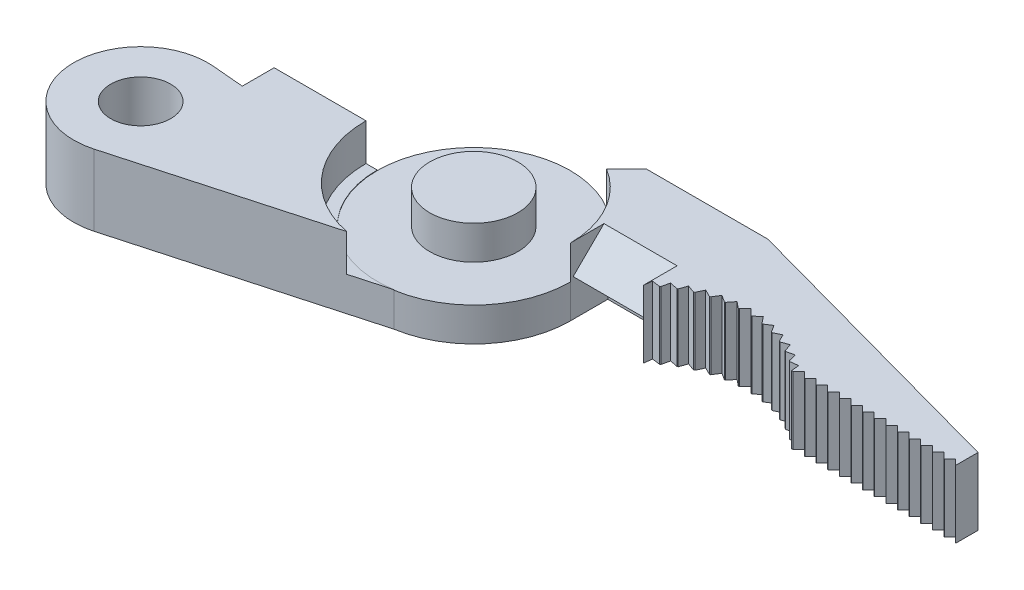
SolidWorks part; units mm, degrees
ref_plane "Front Plane" through (0, 0, 0) normal (0, 0, 1) x (1, 0, 0)
ref_plane "Top Plane" through (0, 0, 0) normal (0, 1, 0) x (1, 0, 0)
ref_plane "Right Plane" through (0, 0, 0) normal (1, 0, 0) x (0, 0, -1)
sketch "Sketch1" plane through (0, 0, 0) normal (0, 1, 0) x (1, 0, 0)
  circle A0 centre (0, 0) radius 6.5405
  circle A1 centre (0, 0) radius 2.9845
  dimension "D1" = 13.081
  dimension "D2" = 5.969
extrude "Boss-Extrude1" add sketch "Sketch1" along normal blind 4.826
sketch "Sketch2" plane through (0, 0, 0) normal (0, 1, 0) x (1, 0, 0)
  line L0 (-6.5405, 0) -> (-13.5255, 0)
  line L1 (-13.5255, 0) -> (-13.5255, -2.159)
  line L2 (-15.6763, -1.9708) -> (-13.5255, -2.159)
  line L3 (1.0584, -6.4543) -> (-14.8567, -10.8736)
  circle A1 centre (-16.0722, -6.4964) radius 2.032
  circle A2 centre (0, 0) radius 2.9845 construction
  arc A3 (-15.6763, -1.9708) -> (-14.8567, -10.8736) centre (-16.0722, -6.4964) ccw
  arc A4 (-6.5405, 0) -> (1.0584, -6.4543) centre (0, 0) ccw
  dimension "D1" = 4.064
  dimension "D6" = 17.3355
  dimension "D2" = 6.985
  dimension "D3" = 2.159
  dimension "D4" = 2.159
  dimension "D5" = 85
extrude "Boss-Extrude2" add sketch "Sketch2" along normal up to surface (4.826 mm away) up to face at (0, 4.826, 6.5405)
hole_wizard "#43 (0.089) Diameter Hole1" positions "Sketch6" profile "Sketch7" hole size "#43" standard "ANSI Inch"
sketch "Sketch6" plane through (0, 0, 0) normal (0, 0, -1) x (-1, 0, 0)
  line L0 (13.5255, 4.826) -> (13.5255, 0) construction
  line L1 (6.5405, 0) -> (13.5255, 0) construction
  point P0 (10.033, 2.413)
  dimension "D1" = 3.4925
  dimension "D2" = 2.413
sketch "Sketch7" plane through (-10.033, 2.413, 0) normal (1, 0, 0) x (0, 1, 0)
  line L0 (0, 0) -> (0, 2.7112)
  line L1 (0, 2.7112) -> (1.1303, 2.032)
  line L2 (1.1303, 2.032) -> (1.1303, 0)
  line L5 (1.1303, 0) -> (0, 0)
  line L10 (0, 2.7112) -> (-1.1303, 2.032) construction
  line L11 (0, -6.35) -> (0, 107.95) construction
  dimension "Hole Dia." = 2.2606
  dimension "Hole Depth" = 2.032
  dimension "Drill Angle" = 118
sketch "Sketch8" plane through (0, 0, 0) normal (0, 1, 0) x (1, 0, 0)
  line L0 (13.0016, 6.9215) -> (32.639, 1.524)
  line L1 (32.639, 1.524) -> (32.639, 0)
  line L2 (32.639, 0) -> (21.5265, 0)
  line L3 (13.0016, 6.9215) -> (4.7466, 6.9215)
  line L4 (4.7466, 6.9215) -> (3.4077, 5.5826)
  line L5 (6.5405, 0) -> (11.4935, 0)
  arc A2 (1.0584, -6.4543) -> (-6.5405, 0) centre (0, 0) ccw construction
  arc A4 (21.5265, 0) -> (11.4935, 0) centre (16.51, -5.7358) ccw
  arc A5 (6.5405, 0) -> (3.4077, 5.5826) centre (0, 0) ccw
  dimension "D1" = 0.381
  dimension "D8" = 15.24
  dimension "D2" = 1.524
  dimension "D3" = 8.255
  dimension "D4" = 32.639
  dimension "D5" = 225
  dimension "D6" = 11.1125
  dimension "D7" = 4.953
extrude "Boss-Extrude3" add sketch "Sketch8" along normal up to surface (4.826 mm away) up to face at (-10.2367, 4.826, 2.2894)
sketch "Sketch9" plane through (0, 4.826, 0) normal (0, 1, 0) x (1, 0, 0)
  line L10 (-7.3025, 0) -> (-6.5405, 0)
  line L11 (-1.463, -7.1544) -> (1.0584, -6.4543)
  line L12 (-14.8567, -10.8736) -> (1.0584, -6.4543) construction
  line L32 (33.401, -0.762) -> (33.401, 2.1048)
  arc A4 (-7.3025, 0) -> (-1.463, -7.1544) centre (0, 0) ccw
  arc A5 (-6.5405, 0) -> (1.0584, -6.4543) centre (0, 0) ccw
  arc A6 (3.4077, 5.5826) -> (-6.5405, 0) centre (0, 0) ccw construction
  arc A7 (1.0584, -6.4543) -> (6.5405, 0) centre (0, 0) ccw construction
  line M26 (-6.5405, 0) -> (-13.5255, 0)
  line M30 (-14.8567, -10.8736) -> (1.0584, -6.4543)
  dimension "D1" = 0.762
  dimension "D2" = 6.5405
  dimension "D3" = 2.6168
extrude "Cut-Extrude1" cut sketch "Sketch9" against normal blind 2.5082 contours A5 A4 M26 M30 region at (-6.9215, 4.826, 0.11)
sketch "Sketch10" plane through (0, 4.826, 0) normal (0, 1, 0) x (1, 0, 0)
  line L0 (32.639, 0) -> (32.258, 0.381)
  line L1 (32.258, 0.381) -> (31.877, 0)
  line L3 (21.5265, 0) -> (32.639, 0) construction
  line L4 (31.877, 0) -> (32.639, 0)
  dimension "D1" = 0.381
extrude "Cut-Extrude2" cut sketch "Sketch10" against normal through all
pattern_linear "LPattern1" count 14 spacing 0.7874 along (-1, 0, 0) of "Cut-Extrude2"
sketch "Sketch11" plane through (0, 4.826, 0) normal (0, 1, 0) x (1, 0, 0)
  line L0 (21.5265, 0) -> (21.4646, 0.5466)
  line L1 (21.4646, 0.5466) -> (20.9187, 0.4794)
  arc A0 (21.5265, 0) -> (11.4935, 0) centre (16.51, -5.7358) ccw construction
  arc A1 (21.5265, 0) -> (20.9187, 0.4794) centre (16.51, -5.7358) ccw
  dimension "D1" = 8.001
extrude "Cut-Extrude3" cut sketch "Sketch11" against normal through all
pattern_circular "CirPattern1" count 13 over 76.5 about axis through (16.51, 4.826, 5.7358) along (0, -1, 0) of "Cut-Extrude3" reverse direction yes
sketch "Sketch13" plane through (0, 4.826, 0) normal (0, 1, 0) x (1, 0, 0)
  line L0 (11.4935, 0) -> (11.4935, 2.54)
  line L1 (11.4935, 2.54) -> (6.5405, 2.54)
  line L2 (6.5405, 2.54) -> (6.5405, 0)
  line L3 (6.5405, 0) -> (11.4935, 0)
  dimension "D1" = 2.54
extrude "Cut-Extrude5" cut sketch "Sketch13" against normal blind 2.5082
sketch "Sketch14" plane through (6.5405, 0, 0) normal (1, 0, 0) x (0, 0, -1)
  line L0 (0, 2.3178) -> (2.54, 4.826)
  line L1 (2.54, 4.826) -> (2.54, 2.3177)
  line L2 (2.54, 2.3177) -> (2.54, 4.826) construction
  line L3 (2.54, 2.3177) -> (0, 2.3178) construction
  line L4 (2.54, 2.3177) -> (0, 2.3178)
extrude "Boss-Extrude4" add sketch "Sketch14" along normal up to next
sketch "Sketch15" plane through (0, 0, 0) normal (0, -1, 0) x (1, 0, 0)
  line L0 (6.5405, 0) -> (6.5405, -2.54)
  line L1 (6.5405, 0) -> (11.4935, 0) construction
  line L2 (6.5405, -2.54) -> (11.52, -2.54)
  line L3 (11.52, -2.54) -> (11.4935, 0)
  line L4 (11.4935, 0) -> (6.5405, 0)
  arc A0 (6.5405, 0) -> (1.0584, 6.4543) centre (0, 0) ccw construction
  dimension "D1" = 2.54
extrude "Cut-Extrude6" cut sketch "Sketch15" against normal blind 2.5082
sketch "Sketch16" plane through (0, 4.826, 0) normal (0, 1, 0) x (1, 0, 0)
  circle A0 centre (0, 0) radius 6.5405
extrude "Cut-Extrude7" cut sketch "Sketch16" against normal blind 2.54
sketch "Sketch18" plane through (0, 0, 0) normal (0, 1, 0) x (1, 0, 0)
  circle A0 centre (0, 0) radius 2.9845
extrude "Boss-Extrude5" add sketch "Sketch18" along normal blind 4.572
sketch "Sketch19" plane through (0, 4.826, 0) normal (0, 1, 0) x (1, 0, 0)
  line L76 (6.5405, 0) -> (6.5405, 2.54)
  line L77 (6.5405, 2.54) -> (11.4935, 2.54)
  line L78 (11.4935, 2.54) -> (11.4935, 0)
  line L79 (11.4935, 0) -> (11.4958, 0.002)
  line L80 (11.4958, 0.002) -> (11.5579, 0.5485)
  line L81 (11.5579, 0.5485) -> (12.1038, 0.4811)
  line L82 (12.1639, 0.5233) -> (12.2863, 1.0595)
  line L83 (12.2863, 1.0595) -> (12.8213, 0.9319)
  line L84 (12.8857, 0.9671) -> (13.0669, 1.4865)
  line L85 (13.0669, 1.4865) -> (13.5845, 1.3003)
  line L86 (13.6524, 1.3281) -> (13.8901, 1.8241)
  line L87 (13.8901, 1.8241) -> (14.3838, 1.5816)
  line L88 (14.4544, 1.6017) -> (14.7457, 2.0683)
  line L89 (14.7457, 2.0683) -> (15.2095, 1.7724)
  line L90 (15.2818, 1.7846) -> (15.6232, 2.2159)
  line L91 (15.6232, 2.2159) -> (16.0512, 1.8704)
  line L92 (16.1244, 1.8745) -> (16.5116, 2.2652)
  line L93 (16.5116, 2.2652) -> (16.8986, 1.8743)
  line L94 (16.9718, 1.8702) -> (17.4, 2.2156)
  line L95 (17.4, 2.2156) -> (17.7411, 1.7841)
  line L96 (17.8135, 1.7719) -> (18.2773, 2.0676)
  line L97 (18.2773, 2.0676) -> (18.5685, 1.6009)
  line L98 (18.6391, 1.5807) -> (19.1329, 1.8231)
  line L99 (19.1329, 1.8231) -> (19.3704, 1.327)
  line L100 (19.4383, 1.2991) -> (19.9559, 1.4851)
  line L101 (19.9559, 1.4851) -> (20.1369, 0.9657)
  line L102 (20.2013, 0.9305) -> (20.7364, 1.0579)
  line L103 (20.7364, 1.0579) -> (20.8586, 0.5215)
  line L104 (20.9187, 0.4794) -> (21.4646, 0.5466)
  line L105 (21.4646, 0.5466) -> (21.5265, 0)
  line L106 (21.5265, 0) -> (21.6408, 0)
  line L107 (21.6408, 0) -> (22.0218, 0.381)
  line L108 (22.0218, 0.381) -> (22.4028, 0)
  line L109 (22.4028, 0) -> (22.4282, 0)
  line L110 (22.4282, 0) -> (22.8092, 0.381)
  line L111 (22.8092, 0.381) -> (23.1902, 0)
  line L112 (23.1902, 0) -> (23.2156, 0)
  line L113 (23.2156, 0) -> (23.5966, 0.381)
  line L114 (23.5966, 0.381) -> (23.9776, 0)
  line L115 (23.9776, 0) -> (24.003, 0)
  line L116 (24.003, 0) -> (24.384, 0.381)
  line L117 (24.384, 0.381) -> (24.765, 0)
  line L118 (24.765, 0) -> (24.7904, 0)
  line L119 (24.7904, 0) -> (25.1714, 0.381)
  line L120 (25.1714, 0.381) -> (25.5524, 0)
  line L121 (25.5524, 0) -> (25.5778, 0)
  line L122 (25.5778, 0) -> (25.9588, 0.381)
  line L123 (25.9588, 0.381) -> (26.3398, 0)
  line L124 (26.3398, 0) -> (26.3652, 0)
  line L125 (26.3652, 0) -> (26.7462, 0.381)
  line L126 (26.7462, 0.381) -> (27.1272, 0)
  line L127 (27.1272, 0) -> (27.1526, 0)
  line L128 (27.1526, 0) -> (27.5336, 0.381)
  line L129 (27.5336, 0.381) -> (27.9146, 0)
  line L130 (27.9146, 0) -> (27.94, 0)
  line L131 (27.94, 0) -> (28.321, 0.381)
  line L132 (28.321, 0.381) -> (28.702, 0)
  line L133 (28.702, 0) -> (28.7274, 0)
  line L134 (28.7274, 0) -> (29.1084, 0.381)
  line L135 (29.1084, 0.381) -> (29.4894, 0)
  line L136 (29.4894, 0) -> (29.5148, 0)
  line L137 (29.5148, 0) -> (29.8958, 0.381)
  line L138 (29.8958, 0.381) -> (30.2768, 0)
  line L139 (30.2768, 0) -> (30.3022, 0)
  line L140 (30.3022, 0) -> (30.6832, 0.381)
  line L141 (30.6832, 0.381) -> (31.0642, 0)
  line L142 (31.0642, 0) -> (31.0896, 0)
  line L143 (31.0896, 0) -> (31.4706, 0.381)
  line L144 (31.4706, 0.381) -> (31.8516, 0)
  line L145 (31.8516, 0) -> (31.877, 0)
  line L146 (31.877, 0) -> (32.258, 0.381)
  line L147 (32.258, 0.381) -> (32.639, 0)
  line L148 (32.639, 0) -> (32.639, 1.524)
  line L149 (32.639, 1.524) -> (13.0016, 6.9215)
  line L150 (13.0016, 6.9215) -> (4.7466, 6.9215)
  line L151 (4.7466, 6.9215) -> (3.4077, 5.5826)
  line L152 (6.5405, 0) -> (6.5405, 2.54)
  line L153 (6.5405, 2.54) -> (11.4935, 2.54)
  line L154 (11.4935, 2.54) -> (11.4935, 0)
  line L155 (11.4935, 0) -> (11.4958, 0.002)
  line L156 (11.4958, 0.002) -> (11.5579, 0.5485)
  line L157 (11.5579, 0.5485) -> (12.1038, 0.4811)
  line L158 (12.1639, 0.5233) -> (12.2863, 1.0595)
  line L159 (12.2863, 1.0595) -> (12.8213, 0.9319)
  line L160 (12.8857, 0.9671) -> (13.0669, 1.4865)
  line L161 (13.0669, 1.4865) -> (13.5845, 1.3003)
  line L162 (13.6524, 1.3281) -> (13.8901, 1.8241)
  line L163 (13.8901, 1.8241) -> (14.3838, 1.5816)
  line L164 (14.4544, 1.6017) -> (14.7457, 2.0683)
  line L165 (14.7457, 2.0683) -> (15.2095, 1.7724)
  line L166 (15.2818, 1.7846) -> (15.6232, 2.2159)
  line L167 (15.6232, 2.2159) -> (16.0512, 1.8704)
  line L168 (16.1244, 1.8745) -> (16.5116, 2.2652)
  line L169 (16.5116, 2.2652) -> (16.8986, 1.8743)
  line L170 (16.9718, 1.8702) -> (17.4, 2.2156)
  line L171 (17.4, 2.2156) -> (17.7411, 1.7841)
  line L172 (17.8135, 1.7719) -> (18.2773, 2.0676)
  line L173 (18.2773, 2.0676) -> (18.5685, 1.6009)
  line L174 (18.6391, 1.5807) -> (19.1329, 1.8231)
  line L175 (19.1329, 1.8231) -> (19.3704, 1.327)
  line L176 (19.4383, 1.2991) -> (19.9559, 1.4851)
  line L177 (19.9559, 1.4851) -> (20.1369, 0.9657)
  line L178 (20.2013, 0.9305) -> (20.7364, 1.0579)
  line L179 (20.7364, 1.0579) -> (20.8586, 0.5215)
  line L180 (20.9187, 0.4794) -> (21.4646, 0.5466)
  line L181 (21.4646, 0.5466) -> (21.5265, 0)
  line L182 (21.5265, 0) -> (21.6408, 0)
  line L183 (21.6408, 0) -> (22.0218, 0.381)
  line L184 (22.0218, 0.381) -> (22.4028, 0)
  line L185 (22.4028, 0) -> (22.4282, 0)
  line L186 (22.4282, 0) -> (22.8092, 0.381)
  line L187 (22.8092, 0.381) -> (23.1902, 0)
  line L188 (23.1902, 0) -> (23.2156, 0)
  line L189 (23.2156, 0) -> (23.5966, 0.381)
  line L190 (23.5966, 0.381) -> (23.9776, 0)
  line L191 (23.9776, 0) -> (24.003, 0)
  line L192 (24.003, 0) -> (24.384, 0.381)
  line L193 (24.384, 0.381) -> (24.765, 0)
  line L194 (24.765, 0) -> (24.7904, 0)
  line L195 (24.7904, 0) -> (25.1714, 0.381)
  line L196 (25.1714, 0.381) -> (25.5524, 0)
  line L197 (25.5524, 0) -> (25.5778, 0)
  line L198 (25.5778, 0) -> (25.9588, 0.381)
  line L199 (25.9588, 0.381) -> (26.3398, 0)
  line L200 (26.3398, 0) -> (26.3652, 0)
  line L201 (26.3652, 0) -> (26.7462, 0.381)
  line L202 (26.7462, 0.381) -> (27.1272, 0)
  line L203 (27.1272, 0) -> (27.1526, 0)
  line L204 (27.1526, 0) -> (27.5336, 0.381)
  line L205 (27.5336, 0.381) -> (27.9146, 0)
  line L206 (27.9146, 0) -> (27.94, 0)
  line L207 (27.94, 0) -> (28.321, 0.381)
  line L208 (28.321, 0.381) -> (28.702, 0)
  line L209 (28.702, 0) -> (28.7274, 0)
  line L210 (28.7274, 0) -> (29.1084, 0.381)
  line L211 (29.1084, 0.381) -> (29.4894, 0)
  line L212 (29.4894, 0) -> (29.5148, 0)
  line L213 (29.5148, 0) -> (29.8958, 0.381)
  line L214 (29.8958, 0.381) -> (30.2768, 0)
  line L215 (30.2768, 0) -> (30.3022, 0)
  line L216 (30.3022, 0) -> (30.6832, 0.381)
  line L217 (30.6832, 0.381) -> (31.0642, 0)
  line L218 (31.0642, 0) -> (31.0896, 0)
  line L219 (31.0896, 0) -> (31.4706, 0.381)
  line L220 (31.4706, 0.381) -> (31.8516, 0)
  line L221 (31.8516, 0) -> (31.877, 0)
  line L222 (31.877, 0) -> (32.258, 0.381)
  line L223 (32.258, 0.381) -> (32.639, 0)
  line L224 (32.639, 0) -> (32.639, 1.524)
  line L225 (32.639, 1.524) -> (13.0016, 6.9215)
  line L226 (13.0016, 6.9215) -> (4.7466, 6.9215)
  line L227 (4.7466, 6.9215) -> (3.4077, 5.5826)
  arc A13 (6.5405, 0) -> (3.4077, 5.5826) centre (0, 0) ccw
  arc A14 (12.1639, 0.5233) -> (12.1038, 0.4811) centre (16.51, -5.7358) ccw
  arc A15 (12.8857, 0.9671) -> (12.8213, 0.9319) centre (16.51, -5.7358) ccw
  arc A16 (13.6524, 1.3281) -> (13.5845, 1.3003) centre (16.51, -5.7358) ccw
  arc A17 (14.4544, 1.6017) -> (14.3838, 1.5816) centre (16.51, -5.7358) ccw
  arc A18 (15.2818, 1.7846) -> (15.2095, 1.7724) centre (16.51, -5.7358) ccw
  arc A19 (16.1244, 1.8745) -> (16.0512, 1.8704) centre (16.51, -5.7358) ccw
  arc A20 (16.9718, 1.8702) -> (16.8986, 1.8743) centre (16.51, -5.7358) ccw
  arc A21 (17.8135, 1.7719) -> (17.7411, 1.7841) centre (16.51, -5.7358) ccw
  arc A22 (18.6391, 1.5807) -> (18.5685, 1.6009) centre (16.51, -5.7358) ccw
  arc A23 (19.4383, 1.2991) -> (19.3704, 1.327) centre (16.51, -5.7358) ccw
  arc A24 (20.2013, 0.9305) -> (20.1369, 0.9657) centre (16.51, -5.7358) ccw
  arc A25 (20.9187, 0.4794) -> (20.8586, 0.5215) centre (16.51, -5.7358) ccw
  arc A26 (6.5405, 0) -> (3.4077, 5.5826) centre (0, 0) ccw
  arc A27 (12.1639, 0.5233) -> (12.1038, 0.4811) centre (16.51, -5.7358) ccw
  arc A28 (12.8857, 0.9671) -> (12.8213, 0.9319) centre (16.51, -5.7358) ccw
  arc A29 (13.6524, 1.3281) -> (13.5845, 1.3003) centre (16.51, -5.7358) ccw
  arc A30 (14.4544, 1.6017) -> (14.3838, 1.5816) centre (16.51, -5.7358) ccw
  arc A31 (15.2818, 1.7846) -> (15.2095, 1.7724) centre (16.51, -5.7358) ccw
  arc A32 (16.1244, 1.8745) -> (16.0512, 1.8704) centre (16.51, -5.7358) ccw
  arc A33 (16.9718, 1.8702) -> (16.8986, 1.8743) centre (16.51, -5.7358) ccw
  arc A34 (17.8135, 1.7719) -> (17.7411, 1.7841) centre (16.51, -5.7358) ccw
  arc A35 (18.6391, 1.5807) -> (18.5685, 1.6009) centre (16.51, -5.7358) ccw
  arc A36 (19.4383, 1.2991) -> (19.3704, 1.327) centre (16.51, -5.7358) ccw
  arc A37 (20.2013, 0.9305) -> (20.1369, 0.9657) centre (16.51, -5.7358) ccw
  arc A38 (20.9187, 0.4794) -> (20.8586, 0.5215) centre (16.51, -5.7358) ccw
  dimension "D1" = 0
extrude "Cut-Extrude8" cut sketch "Sketch19" against normal blind 0.254
sketch "Sketch20" plane through (11.4935, 0, 0) normal (1, 0, 0) x (0, 0, -1)
  line L0 (2.54, 4.826) -> (2.2828, 4.572)
  line L1 (2.2828, 4.572) -> (2.54, 4.572)
  line L2 (2.54, 4.572) -> (2.54, 4.826)
extrude "Cut-Extrude9" cut sketch "Sketch20" against normal up to next
